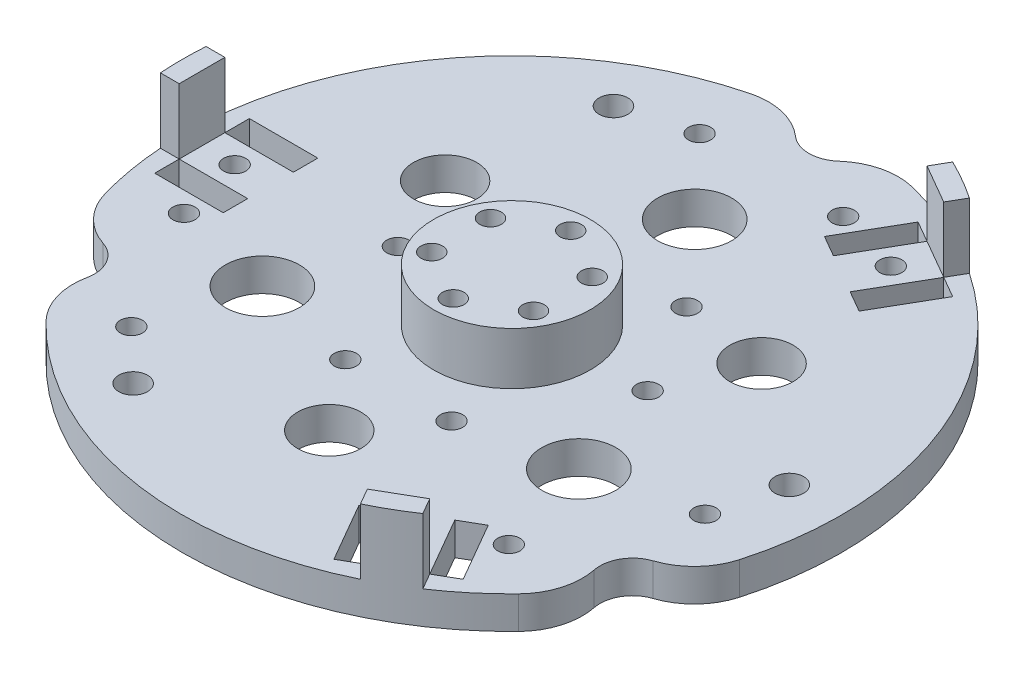
SolidWorks part; units mm, degrees
other "Markup1"
sketch "Sketch12" plane through (-50.5, 13, 50.5) normal (-0.0174, 0.9984, 0.0535) x (0.9946, 0.0227, -0.1009)
ref_plane "Front Plane" through (0, 0, 0) normal (0, 0, 1) x (1, 0, 0)
ref_plane "Top Plane" through (0, 0, 0) normal (0, 1, 0) x (1, 0, 0)
ref_plane "Right Plane" through (0, 0, 0) normal (1, 0, 0) x (0, 0, -1)
sketch "Sketch1" plane through (0, 0, 0) normal (0, 1, 0) x (1, 0, 0)
  circle A0 centre (0, 0) radius 50.5
  dimension "D3" = 101
extrude "Boss-Extrude1" add sketch "Sketch1" along normal blind 5
ref_axis "Axis1" through (0, 15.75, 0) along (0, -1, 0)
sketch "Sketch3" plane through (0, 5, 0) normal (0, 1, 0) x (1, 0, 0)
  line L0 (0, 0) -> (0, 9) construction
  circle A0 centre (0, 0) radius 9 construction
  circle A1 centre (0, 9) radius 1.65
  circle A3 centre (0, 0) radius 12
  circle A4 centre (7.7942, 4.5) radius 1.65
  circle A5 centre (7.7942, -4.5) radius 1.65
  circle A6 centre (0, -9) radius 1.65
  circle A7 centre (-7.7942, -4.5) radius 1.65
  circle A8 centre (-7.7942, 4.5) radius 1.65
  point P18 (0, 0)
  dimension "D1" = 3.3
  dimension "D2" = 6
  dimension "D3" = 24
  dimension "D4" = 18
extrude "Boss-Extrude2" add sketch "Sketch3" along normal blind 8
sketch "Sketch9" plane through (0, 5, 0) normal (0, 1, 0) x (1, 0, 0)
  line L0 (0, 0) -> (0, 50.5) construction
  line L1 (0, 28) -> (0, 15.75) construction
  line L2 (0, 15.75) -> (11, 15.75) construction
  line L3 (-11, 39.75) -> (11, 39.75) construction
  circle A0 centre (0, 0) radius 50.5 construction
  circle A1 centre (0, 28) radius 5.675
  circle A2 centre (11, 15.75) radius 1.7
  circle A5 centre (-11, 15.75) radius 1.7
  circle A6 centre (11, 39.75) radius 1.7
  circle A7 centre (-11, 39.75) radius 1.7
  point P11 (0, 28)
  point P18 (0, 39.75)
  point P32 (0, 0)
  dimension "D1" = 11.35
  dimension "D5" = 3.4
  dimension "D6" = 3.4
  dimension "D3" = 22
  dimension "D4" = 24
  dimension "D2" = 28
  dimension "D7" = 12.25
extrude "Cut-Extrude6" cut sketch "Sketch9" against normal up to next
pattern_circular "CirPattern1" count 3 over 360 about axis through (0, 15.75, 0) along (0, -1, 0) of "Cut-Extrude6" reverse direction yes
sketch "Sketch10" plane through (0, 5, 0) normal (0, 1, 0) x (1, 0, 0)
  line L0 (0, 0) -> (-24.2487, 14) construction
  line L1 (0, 12) -> (0, -12) construction
  line L2 (0, 0) -> (24.2487, 14) construction
  line L3 (0, 0) -> (0, -28) construction
  circle A0 centre (0, 0) radius 12 construction
  circle A1 centre (0, 0) radius 12 construction
  circle A2 centre (-24.2487, 14) radius 4.85
  circle A3 centre (24.2487, 14) radius 4.85
  circle A4 centre (0, -28) radius 4.85
  point P16 (0, 0)
  dimension "D3" = 9.7
  dimension "D1" = 60
  dimension "D2" = 28
  dimension "D4" = 3
extrude "Cut-Extrude7" cut sketch "Sketch10" against normal through all
sketch "Sketch11" plane through (0, 5, 0) normal (0, 1, 0) x (1, 0, 0)
  line L0 (0, 0) -> (21.25, 36.8061) construction
  line L1 (0, 0) -> (0, 50.5) construction
  circle A0 centre (0, 0) radius 50.5 construction
  circle A7 centre (21.25, 36.8061) radius 1.7
  dimension "D2" = 3.4
  dimension "D1" = 42.5
  dimension "D3" = 30
extrude "Cut-Extrude8" cut sketch "Sketch11" against normal through all contours A7
sketch "Sketch13" plane through (0, 5, 0) normal (0, 1, 0) x (1, 0, 0)
  line L0 (0, 0) -> (0, 50.5) construction
  line L1 (0, 0) -> (-21.25, 36.8061) construction
  circle A0 centre (0, 0) radius 50.5 construction
  circle A1 centre (-21.25, 36.8061) radius 2.2
  dimension "D2" = 4.4
  dimension "D1" = 30
  dimension "D3" = 42.5
extrude "Cut-Extrude9" cut sketch "Sketch13" against normal up to next
sketch "Sketch14" plane through (0, 0, 0) normal (0, -1, 0) x (1, 0, 0)
  line L0 (0, 0) -> (0, 46) construction
  line L1 (5, 46) -> (-5, 46) construction
  line L2 (-5, 46) -> (-14.6593, 43.4118) construction
  line L3 (5, 46) -> (14.6593, 43.4118) construction
  circle A2 centre (-14.6593, 43.4118) radius 1.7
  circle A3 centre (14.6593, 43.4118) radius 1.7
  dimension "D1" = 3.4
  dimension "D2" = 10
  dimension "D3" = 5
  dimension "D4" = 46
  dimension "D5" = 165
extrude "Cut-Extrude10" [suppressed] cut sketch "Sketch14" against normal through all
pattern_circular "CirPattern2" count 3 over 360 about axis through (0, 15.75, 0) along (0, -1, 0) of "Cut-Extrude8", "Cut-Extrude9", "Cut-Extrude10"
sketch "Sketch15" plane through (0, 5, 0) normal (0, 1, 0) x (1, 0, 0)
  line L0 (0, 0) -> (21.25, 36.8061) construction
  line L1 (14.75, 25.5477) -> (17.7811, 23.7977) construction
  line L2 (17.7811, 23.7977) -> (26.7811, 39.3862) construction
  line L3 (26.7811, 39.3862) -> (20.7189, 42.8862) construction
  line L4 (20.7189, 42.8862) -> (11.7189, 27.2977) construction
  line L5 (11.7189, 27.2977) -> (14.75, 25.5477) construction
  line L9 (20.7189, 42.8862) -> (17.4713, 44.7612)
  line L10 (17.4713, 44.7612) -> (12.2213, 35.6679)
  line L11 (12.2213, 35.6679) -> (15.4689, 33.7929)
  line L13 (26.7811, 39.3862) -> (30.0287, 37.5112)
  line L14 (30.0287, 37.5112) -> (24.7787, 28.4179)
  line L15 (24.7787, 28.4179) -> (21.5311, 30.2929)
  line L18 (15.4689, 33.7929) -> (20.7189, 42.8862)
  line L19 (21.5311, 30.2929) -> (26.7811, 39.3862)
  dimension "D1" = 7
  dimension "D2" = 3.5
  dimension "D3" = 5
  dimension "D4" = 18
  dimension "D5" = 3.75
  dimension "D6" = 10.5
  dimension "D8" = 3.75
  dimension "D10" = 10.5
extrude "Cut-Extrude11" cut sketch "Sketch15" against normal through all
sketch "Sketch17" plane through (0, 5, 0) normal (0, 1, 0) x (1, 0, 0)
  line L0 (20.7189, 42.8862) -> (26.7811, 39.3862)
  line L1 (26.7811, 39.3862) -> (28.2204, 41.8791)
  line L2 (20.7189, 42.8862) -> (22.1582, 45.3791)
  circle A0 centre (0, 0) radius 50.5 construction
  arc A1 (22.1582, 45.3791) -> (28.2204, 41.8791) centre (0, 0) cw
extrude "Boss-Extrude3" add sketch "Sketch17" along normal blind 10
pattern_circular "CirPattern3" count 3 over 360 about axis through (0, 15.75, 0) along (0, -1, 0) of "Cut-Extrude11", "Boss-Extrude3"
sketch "Sketch18" plane through (0, 5, 0) normal (0, 1, 0) x (1, 0, 0)
  line L0 (0, 0) -> (43.7343, -25.25) construction
  circle A1 centre (24.2487, -14) radius 5.675 construction
  circle A2 centre (0, 0) radius 50.5 construction
  circle A3 centre (24.2487, -14) radius 5.675
  arc A4 (46.0169, -20.8014) -> (41.023, -29.4511) centre (43.7343, -25.25) ccw
  arc A5 (41.023, -29.4511) -> (46.0169, -20.8014) centre (43.7343, -25.25) ccw construction
  arc A6 (41.023, -29.4511) -> (46.0169, -20.8014) centre (0, 0) ccw
  dimension "D1" = 10
extrude "Cut-Extrude12" cut sketch "Sketch18" against normal through all contours A4 region at (41.8584, 5, 24.167)
fillet "Fillet1" radius 10 2 edges at (46.0169, 2.5, 20.8014) (41.023, 2.5, 29.4511)
pattern_circular "CirPattern4" count 3 over 360 about axis through (0, 15.75, 0) along (0, -1, 0) of "Cut-Extrude12", "Fillet1"
